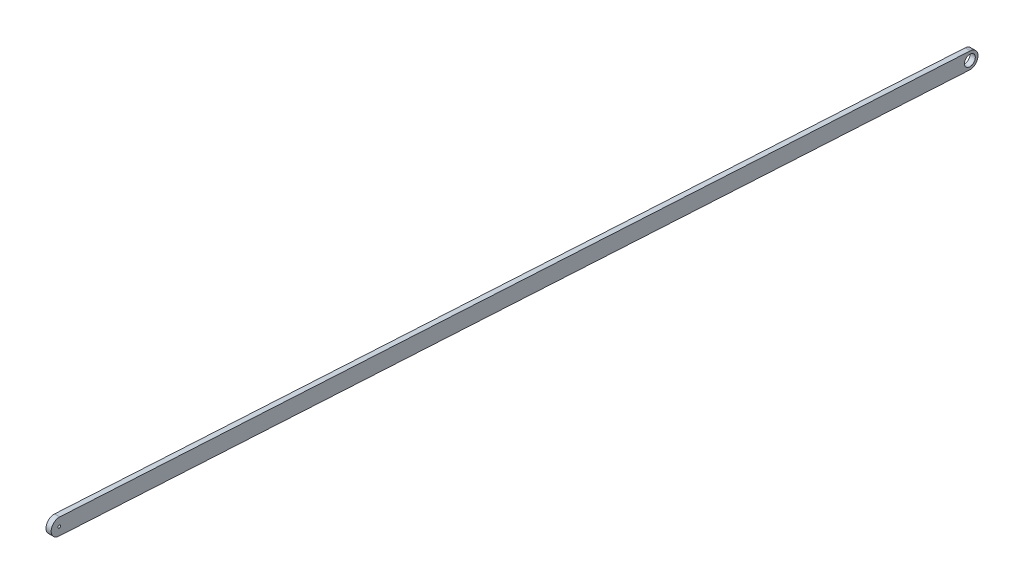
SolidWorks part; units mm, degrees
ref_plane "Front Plane" through (0, 0, 0) normal (0, 0, 1) x (1, 0, 0)
ref_plane "Top Plane" through (0, 0, 0) normal (0, 1, 0) x (1, 0, 0)
ref_plane "Right Plane" through (0, 0, 0) normal (1, 0, 0) x (0, 0, -1)
sketch "Sketch1" plane through (0, 0, 0) normal (1, 0, 0) x (0, 0, -1)
  line L0 (332.9912, -0.5942) -> (-199.3965, 29.5999)
  line L5 (-199.9358, 20.0901) -> (332.4518, -10.1039)
  circle A0 centre (-199.6662, 24.845) radius 0.7938
  circle A1 centre (332.7215, -5.349) radius 3.175
  circle A8 centre (-199.6662, 24.845) radius 0.7937 construction
  circle A9 centre (-199.6662, 24.845) radius 4.7625
  circle A10 centre (332.7215, -5.349) radius 4.7625
  dimension "D4" = 9.525
  dimension "D1" = 6.35
  dimension "D2" = 1.5875
  dimension "D3" = 9.525
extrude "Boss-Extrude1" add sketch "Sketch1" along normal blind 3.0378 contours A9 A0 | A10 L0 A9 L5 | A10 A1 region at (0, 9.748, -66.5277) region at (0, -2.1707, -336.0852) region at (0, 28.0234, 196.3025)
